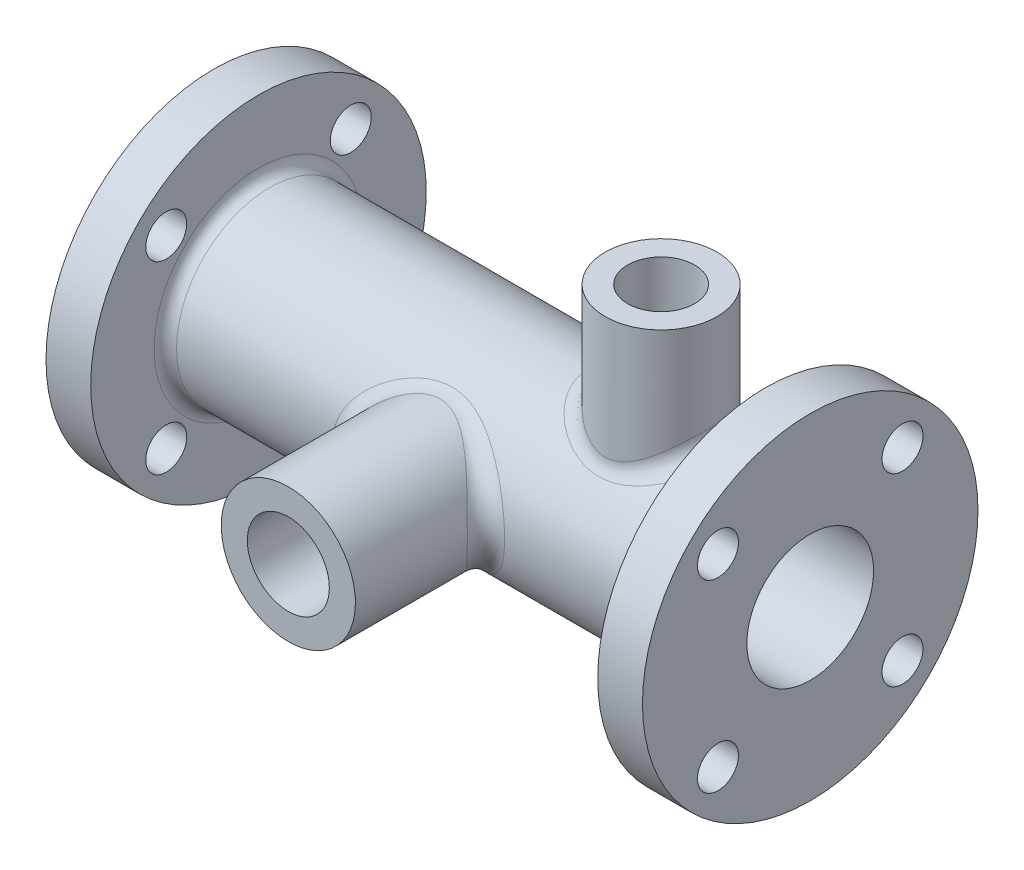
SolidWorks part; units mm, degrees
ref_plane "前视基准面" through (0, 0, 0) normal (0, 0, 1) x (1, 0, 0)
ref_plane "上视基准面" through (0, 0, 0) normal (0, 1, 0) x (1, 0, 0)
ref_plane "右视基准面" through (0, 0, 0) normal (1, 0, 0) x (0, 0, -1)
ref_plane "基准面1" through (-80, 0, 0) normal (1, 0, 0) x (0, 0, -1)
sketch "草图1" plane through (-80, 0, 0) normal (1, 0, 0) x (0, 0, -1)
  circle A0 centre (0, 0) radius 25
extrude "凸台-拉伸1" add sketch "草图1" along normal blind 160
sketch "草图2" plane through (-80, 0, 0) normal (1, 0, 0) x (0, 0, -1)
  circle A0 centre (0, 0) radius 45
extrude "凸台-拉伸2" add sketch "草图2" along normal blind 12
ref_plane "基准面2" through (68, 0, 0) normal (1, 0, 0) x (0, 0, -1)
sketch "草图3" plane through (68, 0, 0) normal (1, 0, 0) x (0, 0, -1)
  circle A0 centre (0, 0) radius 45
extrude "凸台-拉伸3" add sketch "草图3" along normal blind 12
sketch "草图4" plane through (0, 0, 0) normal (0, 0, 1) x (1, 0, 0)
  circle A0 centre (0, 0) radius 18
extrude "凸台-拉伸4" add sketch "草图4" along normal blind 60
sketch "草图5" plane through (0, 0, 0) normal (0, 1, 0) x (1, 0, 0)
  circle A0 centre (40, 0) radius 15
extrude "凸台-拉伸5" add sketch "草图5" along normal blind 55
fillet "圆角1" radius 5 2 edges at (39.9676, 20, 15) (-17.7147, -3.1921, 24.7954)
fillet "圆角2" radius 3 2 edges at (68, 0, -25) (-68, 0, -25)
sketch "草图6" plane through (-80, 0, 0) normal (1, 0, 0) x (0, 0, -1)
  circle A0 centre (0, 0) radius 17
extrude "切除-拉伸1" cut sketch "草图6" along normal through all
ref_plane "基准面3" through (0, 0, 60) normal (0, 0, 1) x (1, 0, 0)
sketch "草图7" plane through (0, 0, 60) normal (0, 0, 1) x (1, 0, 0)
  circle A0 centre (0, 0) radius 11
extrude "切除-拉伸2" cut sketch "草图7" against normal blind 60
ref_plane "基准面4" through (0, 55, 0) normal (0, 1, 0) x (1, 0, 0)
sketch "草图8" plane through (0, 55, 0) normal (0, 1, 0) x (1, 0, 0)
  circle A0 centre (40, 0) radius 9
extrude "切除-拉伸3" cut sketch "草图8" against normal blind 55
sketch "草图9" plane through (-80, 0, 0) normal (1, 0, 0) x (0, 0, -1)
  circle A0 centre (-24.7487, 24.7487) radius 5.5
  circle A1 centre (24.7487, 24.7487) radius 5.5
  circle A2 centre (24.7487, -24.7487) radius 5.5
  circle A3 centre (-24.7487, -24.7487) radius 5.5
extrude "切除-拉伸4" cut sketch "草图9" along normal through all
